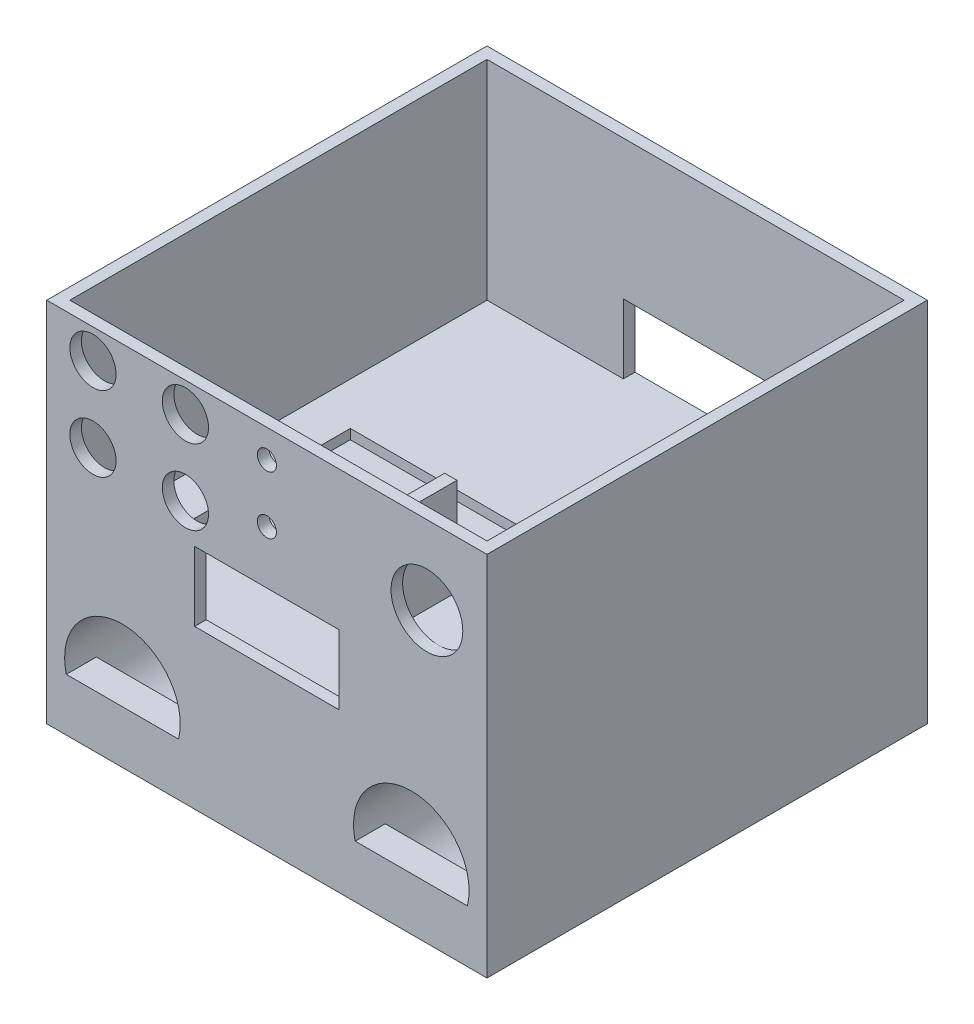
SolidWorks part; units mm, degrees
ref_plane "Front Plane" through (0, 0, 0) normal (0, 0, 1) x (1, 0, 0)
ref_plane "Top Plane" through (0, 0, 0) normal (0, 1, 0) x (1, 0, 0)
ref_plane "Right Plane" through (0, 0, 0) normal (1, 0, 0) x (0, 0, -1)
sketch "Sketch1" plane through (0, 0, 0) normal (0, 1, 0) x (1, 0, 0)
  line L1 (0, 76.2) -> (76.2, 76.2)
  line L2 (0, 76.2) -> (0, 0)
  line L3 (0, 0) -> (76.2, 0)
  line L4 (76.2, 76.2) -> (76.2, 0)
  dimension "D1" = 76.2
  dimension "D2" = 76.2
extrude "Boss-Extrude1" add sketch "Sketch1" along normal blind 38.1
shell "Shell1" thickness 2 removed face at (38.1, 38.1, -38.1)
sketch "Sketch2" plane through (0, 0, 0) normal (0, 0, 1) x (1, 0, 0)
  line L0 (0, 0) -> (76.2, 0) construction
  line L1 (25.6, 14) -> (50.6, 14)
  line L2 (25.6, 14) -> (25.6, 2)
  line L3 (25.6, 2) -> (50.6, 2)
  line L4 (50.6, 14) -> (50.6, 2)
  point P4 (38.1, 2)
  point P7 (38.1, 0)
  dimension "D1" = 12
  dimension "D2" = 25
  dimension "D3" = 2
extrude "Cut-Extrude1" cut sketch "Sketch2" against normal through all
sketch "Sketch3" plane through (0, 0, 0) normal (0, 0, 1) x (1, 0, 0)
  line L0 (0, 0) -> (76.2, 0) construction
  line L1 (0, 38.1) -> (0, 0) construction
  circle A0 centre (24, 20) radius 4
  circle A1 centre (8, 20) radius 4
  circle A2 centre (24, 33) radius 4
  circle A3 centre (8, 33) radius 4
  dimension "D2" = 8
  dimension "D4" = 8
  dimension "D1" = 16
  dimension "D3" = 20
  dimension "D5" = 13
extrude "Cut-Extrude2" cut sketch "Sketch3" against normal up to next
sketch "Sketch4" plane through (0, 0, 0) normal (0, 0, 1) x (1, 0, 0)
  line L0 (76.2, 38.1) -> (76.2, 0) construction
  line L2 (0, 38.1) -> (76.2, 38.1) construction
  circle A0 centre (65.8, 24.5) radius 6.2103
  dimension "D1" = 12.4206
  dimension "D2" = 10.4
  dimension "D3" = 13.6
extrude "Cut-Extrude3" cut sketch "Sketch4" against normal up to next
sketch "Sketch6" plane through (0, 0, 0) normal (0, 0, 1) x (1, 0, 0)
  line L0 (0, 38.1) -> (76.2, 38.1) construction
  line L2 (38.1, 33.2) -> (38.1, 23.2) construction
  circle A0 centre (38.1, 23.2) radius 1.65
  circle A1 centre (38.1, 33.2) radius 1.65
  point P6 (38.1, 38.1)
  dimension "D1" = 3.3
  dimension "D2" = 10
  dimension "D3" = 4.9
extrude "Cut-Extrude4" cut sketch "Sketch6" against normal up to next
extrude "Boss-Extrude2" add sketch "Sketch1<2>" against normal blind 25.4
sketch "Sketch1<2>" plane through (0, 0, 0) normal (0, 1, 0) x (1, 0, 0) same geometry as "Sketch1"
sketch "Sketch11" plane through (0, 0, -76.2) normal (0, 0, -1) x (-1, 0, 0)
  line L0 (-63.1, -13.9) -> (-13.1, -13.9) construction
  line L1 (-76.2, -25.4) -> (0, -25.4) construction
  circle A0 centre (-63.1, -13.9) radius 10
  circle A1 centre (-13.1, -13.9) radius 10
  point P6 (-38.1, -25.4)
  point P7 (-38.1, -13.9)
  dimension "D1" = 20
  dimension "D2" = 50
  dimension "D3" = 11.5
extrude "Cut-Extrude6" cut sketch "Sketch11" against normal blind 71
sketch "Sketch15" plane through (0, 0, -5.2) normal (0, 0, -1) x (-1, 0, 0)
  line L0 (-72.81, -16.2909) -> (-53.39, -16.2909)
  line L1 (-22.81, -16.2909) -> (-3.39, -16.2909)
  arc A0 (-53.39, -16.2909) -> (-72.81, -16.2909) centre (-63.1, -13.9) ccw
  circle A1 centre (-63.1, -13.9) radius 10 construction
  arc A2 (-3.39, -16.2909) -> (-22.81, -16.2909) centre (-13.1, -13.9) ccw
  circle A3 centre (-13.1, -13.9) radius 10 construction
extrude "Cut-Extrude8" cut sketch "Sketch15" against normal up to next
sketch "Sketch16" plane through (0, 2, 0) normal (0, 1, 0) x (1, 0, 0)
  line L0 (50.6, 2) -> (60.7, 2) construction
  line L2 (50.6, 2) -> (74.2, 2) construction
  line L13 (60.7, 2) -> (9.392, 2)
  line L14 (60.7, 2) -> (60.7, 43.148)
  line L15 (60.7, 43.148) -> (9.392, 43.148)
  line L16 (9.392, 2) -> (9.392, 43.148)
  dimension "D1" = 10.1
  dimension "D2" = 51.308
  dimension "D3" = 41.148
extrude "Cut-Extrude9" cut sketch "Sketch16" against normal blind 1.7
sketch "Sketch19" plane through (0, 0, -2) normal (0, 0, -1) x (-1, 0, 0)
  line L0 (-65.8, 18.2897) -> (-65.8, 34.9267) construction
  line L1 (-2, 38.1) -> (-74.2, 38.1) construction
  line L2 (-74.2, 38.1) -> (-74.2, 2) construction
  line L4 (-59.323, 34.9267) -> (-59.323, 18.1867)
  line L5 (-59.323, 18.1867) -> (-72.277, 18.1867)
  line L6 (-72.277, 34.9267) -> (-72.277, 18.1867)
  line L7 (-74.2, 34.9267) -> (-72.277, 34.9267)
  line L8 (-74.2, 34.9267) -> (-74.2, 15.7428)
  line L9 (-74.2, 15.7428) -> (-57.2, 15.7428)
  line L10 (-57.2, 34.9267) -> (-57.2, 15.7428)
  line L11 (-59.323, 34.9267) -> (-57.2, 34.9267)
  circle A0 centre (-65.8, 24.5) radius 6.2103 construction
  dimension "D1" = 16.637
  dimension "D2" = 6.477
  dimension "D3" = 12.954
  dimension "D4" = 16.74
  dimension "D5" = 17
  dimension "D6" = 19.1839
  dimension "D7" = 3.1733
extrude "Boss-Extrude3" add sketch "Sketch19" along normal blind 9.6774
